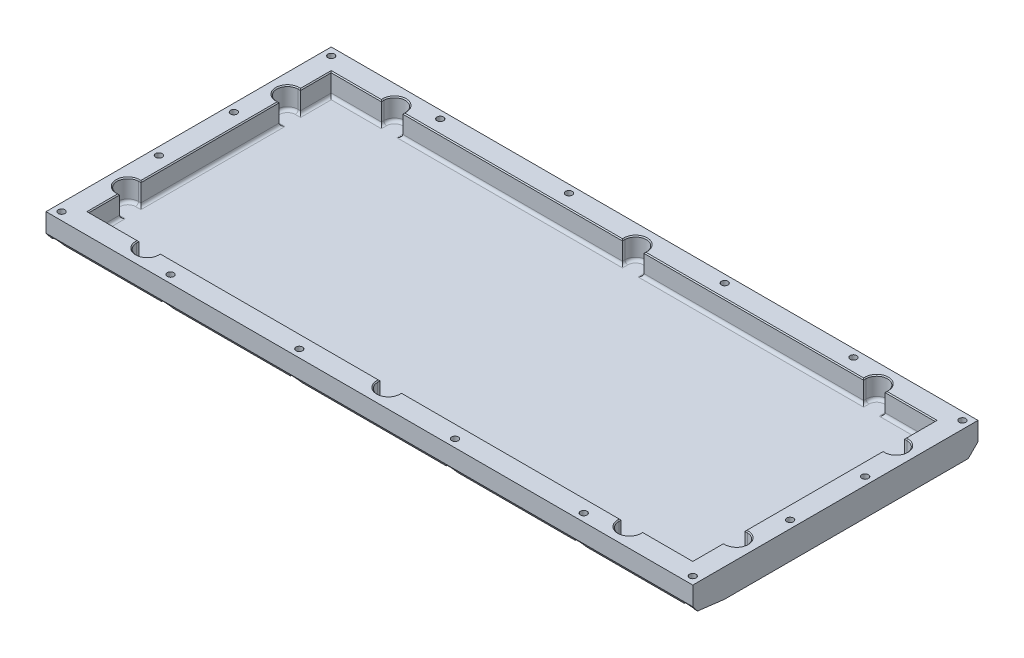
SolidWorks part; units mm, degrees
note: The reader was unsure of these and kept them because the rebuilt part matched: shared geometry of "Sketch4<3>", "Sketch6<2>".
material "7075-T6 (SN)"
ref_plane "Front Plane" through (0, 0, 0) normal (0, 0, 1) x (1, 0, 0)
ref_plane "Top Plane" through (0, 0, 0) normal (0, 1, 0) x (1, 0, 0)
ref_plane "Right Plane" through (0, 0, 0) normal (1, 0, 0) x (0, 0, -1)
sketch "Sketch1" plane through (0, 0, 0) normal (0, 1, 0) x (1, 0, 0)
  line L1 (-166.1375, 73.2688) -> (166.1375, 73.2688)
  line L2 (-166.1375, 73.2688) -> (-166.1375, -73.2688)
  line L3 (-166.1375, -73.2688) -> (166.1375, -73.2688)
  line L4 (166.1375, 73.2688) -> (166.1375, -73.2688)
  point P4 (0, 73.2688)
  point P6 (166.1375, 0)
  dimension "D1" = 146.5376
  dimension "D2" = 332.275
extrude "Boss-Extrude1" add sketch "Sketch1" against normal blind 15
sketch "Sketch4" plane through (166.1375, 0, 0) normal (1, 0, 0) x (0, 0, -1)
  line L0 (-73.2688, -12.5) -> (73.2688, -30.4926)
  line L1 (-73.2688, -15) -> (-73.2688, 0) construction
  line L2 (73.2688, -30.4926) -> (73.2688, -15)
  line L3 (73.2688, -15) -> (73.2688, 0) construction
  line L4 (-73.2688, 0) -> (73.2688, 0) construction
  line L5 (73.2688, -15) -> (-73.2688, -15)
  line L6 (-73.2688, -15) -> (-73.2688, -12.5)
  line M4 (-73.2688, 0) -> (-73.2688, -15)
  line M5 (-73.2688, -15) -> (73.2688, -15)
  dimension "D1" = 7
  dimension "D2" = 12.5
extrude "Cut-Extrude1" cut sketch "Sketch4" against normal through all contours L0 M4 M5
extrude "Boss-Extrude2" add sketch "Sketch4<3>" against normal up to surface (332.275 mm away) contours L0 L2 M5 up to face at (-166.1375, -8.5, 10.5816)
sketch "Sketch4<3>" plane through (166.1375, 0, 0) normal (1, 0, 0) x (0, 0, -1) same geometry as "Sketch4"
sketch "Sketch6" plane through (-166.1375, 0, 0) normal (-1, 0, 0) x (0, 0, 1)
  line L1 (-73.2688, 0) -> (73.2688, 0) construction
  line L3 (-73.2688, -14.5) -> (56.9801, -14.5)
  line L7 (-73.2688, 0) -> (-73.2688, -30.4926)
  line L8 (-73.2688, -30.4926) -> (73.2688, -12.5)
  line L9 (73.2688, -12.5) -> (73.2688, 0)
  line L10 (73.2688, 0) -> (-73.2688, 0)
  line L11 (-73.2688, -14.5) -> (-73.2688, -30.4926)
  line L12 (-73.2688, -30.4926) -> (56.9801, -14.5)
  point P0 (-77.4503, -15.2463)
  dimension "D1" = 14.5
  dimension "D2" = 0
extrude "Cut-Extrude3" cut sketch "Sketch6" against normal blind 75
extrude "Cut-Extrude4" cut sketch "Sketch6<2>" along normal blind 75 from surface at -332.275
sketch "Sketch6<2>" plane through (-166.1375, 0, 0) normal (-1, 0, 0) x (0, 0, 1) same geometry as "Sketch6"
chamfer "Chamfer3" distance 5 angle 45 3 edges at (128.6375, -14.5, -73.2688) (0, -30.4926, -73.2688) (-128.6375, -14.5, -73.2688)
chamfer "Chamfer4" distance 0.5 angle 45 2 edges at (91.1375, -22.2229, -5.9177) (-91.1375, -22.2229, -5.9177)
chamfer "Chamfer5" distance 2.5 angle 45 1 edges at (0, -12.5, 73.2688)
hole_wizard "M3 Clearance Hole1" positions "Sketch7" profile "Sketch8" hole size "M3" standard "DIN" end condition through all
sketch "Sketch7" plane through (0, 0, 0) normal (0, 1, 0) x (1, 0, 0)
  line L0 (166.1375, 73.2688) -> (-166.1375, 73.2688) construction
  line L1 (-166.1375, 73.2688) -> (-166.1375, -73.2688) construction
  line L2 (0, 0) -> (0, 73.2688) construction
  line L5 (0, 0) -> (-166.1375, 0) construction
  line L6 (-166.1375, -73.2688) -> (166.1375, -73.2688) construction
  point P0 (-162.1375, 69.2688)
  point P21 (-106.1375, 69.2688)
  point P23 (-40, 69.2688)
  point P28 (-162.1375, -69.2688)
  point P34 (-162.1375, -19.2688)
  point P36 (-162.1375, 19.2688)
  point P39 (0, 0)
  point P40 (0, 0)
  point P41 (162.1375, 19.2688)
  point P42 (162.1375, -19.2688)
  point P43 (162.1375, -69.2688)
  point P44 (40, 69.2688)
  point P45 (106.1375, 69.2688)
  point P46 (162.1375, 69.2688)
  point P47 (0, 0)
  point P48 (106.1375, -69.2688)
  point P49 (40, -69.2688)
  point P51 (-40, -69.2688)
  point P52 (-106.1375, -69.2688)
  point P53 (0, 0)
  point P54 (0, 0)
  dimension "D1" = 4
  dimension "D2" = 4
  dimension "D3" = 56
  dimension "D4" = 40
  dimension "D5" = 4
  dimension "D6" = 50
  dimension "D7" = 50
sketch "Sketch8" plane through (-162.1375, 0, -69.2688) normal (1, 0, 0) x (0, 0, 1)
  line L0 (0, 0) -> (0, 29.9458)
  line L1 (0, 29.9458) -> (1.7, 29.9458)
  line L2 (1.7, 29.9458) -> (1.7, 0)
  line L5 (1.7, 0) -> (0, 0)
  line L11 (0, -6.35) -> (0, 107.95) construction
  dimension "Thru Hole Dia." = 3.4
  dimension "Thru Hole Depth" = 29.9458
sketch "Sketch9" plane through (0, -14.5, 0) normal (0, -1, 0) x (1, 0, 0)
  circle A0 centre (-162.1375, 69.2688) radius 3.25
  circle A1 centre (-162.1375, 19.2688) radius 3.25
  circle A2 centre (-162.1375, -19.2688) radius 3.25
  circle A3 centre (-162.1375, -69.2688) radius 3.25
  circle A4 centre (-106.1375, -69.2688) radius 3.25
  circle A5 centre (-40, -69.2688) radius 3.25
  circle A7 centre (40, -69.2688) radius 3.25
  circle A8 centre (106.1375, -69.2688) radius 3.25
  circle A9 centre (162.1375, -69.2688) radius 3.25
  circle A10 centre (162.1375, -19.2688) radius 3.25
  circle A11 centre (162.1375, 19.2688) radius 3.25
  circle A12 centre (162.1375, 69.2688) radius 3.25
  circle A13 centre (106.1375, 69.2688) radius 3.25
  circle A14 centre (40, 69.2688) radius 3.25
  circle A16 centre (-40, 69.2688) radius 3.25
  circle A17 centre (-106.1375, 69.2688) radius 3.25
  dimension "D1" = 6.5
extrude "Cut-Extrude5" cut sketch "Sketch9" against normal offset from surface 4 and the other way through all up to face at (-162.1375, 0, -67.5688)
fillet "Fillet2" radius 3 2 edges at (91.1375, -14.5, -7.6957) (-91.1375, -14.5, -7.6957)
sketch "Sketch5" plane through (0, 0, 1.305) normal (0, -1, 0) x (1, 0, 0)
  line L0 (166.1375, -74.5738) -> (-166.1375, -74.5738) construction
  line L1 (-155.1375, -63.5738) -> (155.1375, -63.5738)
  line L2 (-155.1375, -63.5738) -> (-155.1375, 60.9638)
  line L3 (-155.1375, 60.9638) -> (155.1375, 60.9638)
  line L4 (155.1375, -63.5738) -> (155.1375, 60.9638)
  line L5 (-166.1375, -74.5738) -> (-166.1375, 71.9638) construction
  point P4 (0, -63.5738)
  point P6 (155.1375, -1.305)
  dimension "D1" = 11
  dimension "D2" = 11
extrude "Cut-Extrude2" cut sketch "Sketch5" along normal blind 11 from surface at 0 starting at face at (-162.1375, 0, -67.5688)
sketch "Sketch10" plane through (0, 0, 0) normal (0, 1, 0) x (1, 0, 0)
  line L0 (-129.375, 63.5063) -> (-129.375, 62.2688)
  line L1 (155.1375, 62.2688) -> (-155.1375, 62.2688) construction
  line L2 (-129.375, 62.2688) -> (-118.375, 62.2688)
  line L3 (-118.375, 62.2688) -> (-118.375, 63.5063)
  line L4 (-156.375, 46.5063) -> (-155.1375, 46.5063)
  line L5 (-155.1375, 62.2688) -> (-155.1375, -62.2688) construction
  line L6 (-155.1375, 46.5063) -> (-155.1375, 35.5063)
  line L7 (-155.1375, 62.2688) -> (-155.1375, -62.2688) construction
  line L8 (-155.1375, 35.5063) -> (-156.375, 35.5063)
  line L9 (-5.5, 63.5063) -> (-5.5, 62.2688)
  line L10 (-5.5, 62.2688) -> (5.5, 62.2688)
  line L11 (5.5, 62.2688) -> (5.5, 63.5063)
  line L12 (129.375, 63.5063) -> (129.375, 62.2688)
  line L13 (129.375, 62.2688) -> (118.375, 62.2688)
  line L14 (118.375, 62.2688) -> (118.375, 63.5063)
  line L15 (156.375, 46.5063) -> (155.1375, 46.5063)
  line L16 (155.1375, -62.2688) -> (155.1375, 62.2688) construction
  line L17 (155.1375, 46.5063) -> (155.1375, 35.5063)
  line L18 (155.1375, -62.2688) -> (155.1375, 62.2688) construction
  line L19 (155.1375, 35.5063) -> (156.375, 35.5063)
  line L20 (156.375, -35.5062) -> (155.1375, -35.5062)
  line L21 (155.1375, -35.5062) -> (155.1375, -46.5062)
  line L22 (155.1375, -46.5062) -> (156.375, -46.5062)
  line L23 (129.375, -63.5062) -> (129.375, -62.2688)
  line L24 (-155.1375, -62.2688) -> (155.1375, -62.2688) construction
  line L25 (129.375, -62.2688) -> (118.375, -62.2688)
  line L26 (118.375, -62.2688) -> (118.375, -63.5062)
  line L27 (-5.5, -63.5062) -> (-5.5, -62.2688)
  line L28 (-5.5, -62.2688) -> (5.5, -62.2688)
  line L29 (5.5, -62.2688) -> (5.5, -63.5062)
  line L30 (-129.375, -63.5062) -> (-129.375, -62.2688)
  line L31 (-129.375, -62.2688) -> (-118.375, -62.2688)
  line L32 (-118.375, -62.2688) -> (-118.375, -63.5062)
  line L33 (-156.375, -46.5062) -> (-155.1375, -46.5062)
  line L34 (-155.1375, -46.5062) -> (-155.1375, -35.5062)
  line L35 (-155.1375, -35.5062) -> (-156.375, -35.5062)
  arc A16 (-156.375, 46.5063) -> (-156.375, 35.5063) centre (-156.375, 41.0063) ccw
  arc A17 (-156.375, 46.5063) -> (-156.375, 35.5063) centre (-156.375, 41.0063) ccw
  arc A19 (-118.375, 63.5063) -> (-129.375, 63.5063) centre (-123.875, 63.5063) ccw
  arc A20 (-118.375, 63.5063) -> (-129.375, 63.5063) centre (-123.875, 63.5063) ccw
  arc A22 (-156.375, -35.5062) -> (-156.375, -46.5062) centre (-156.375, -41.0062) ccw
  arc A23 (-156.375, -35.5062) -> (-156.375, -46.5062) centre (-156.375, -41.0062) ccw
  arc A25 (-129.375, -63.5062) -> (-118.375, -63.5062) centre (-123.875, -63.5062) ccw
  arc A26 (-129.375, -63.5062) -> (-118.375, -63.5062) centre (-123.875, -63.5062) ccw
  arc A28 (-5.5, -63.5062) -> (5.5, -63.5062) centre (0, -63.5062) ccw
  arc A29 (-5.5, -63.5062) -> (5.5, -63.5062) centre (0, -63.5062) ccw
  arc A31 (5.5, 63.5063) -> (-5.5, 63.5063) centre (0, 63.5063) ccw
  arc A32 (5.5, 63.5063) -> (-5.5, 63.5063) centre (0, 63.5063) ccw
  arc A34 (129.375, 63.5063) -> (118.375, 63.5063) centre (123.875, 63.5063) ccw
  arc A35 (129.375, 63.5063) -> (118.375, 63.5063) centre (123.875, 63.5063) ccw
  arc A37 (156.375, 35.5063) -> (156.375, 46.5063) centre (156.375, 41.0063) ccw
  arc A38 (156.375, 35.5063) -> (156.375, 46.5063) centre (156.375, 41.0063) ccw
  arc A40 (118.375, -63.5062) -> (129.375, -63.5062) centre (123.875, -63.5062) ccw
  arc A41 (118.375, -63.5062) -> (129.375, -63.5062) centre (123.875, -63.5062) ccw
  arc A43 (156.375, -46.5062) -> (156.375, -35.5062) centre (156.375, -41.0062) ccw
  arc A44 (156.375, -46.5062) -> (156.375, -35.5062) centre (156.375, -41.0062) ccw
  dimension "D1" = 1
  dimension "D2" = 1
  dimension "D3" = 1
  dimension "D4" = 1
  dimension "D5" = 1
  dimension "D6" = 1
  dimension "D7" = 1
  dimension "D8" = 1
  dimension "D9" = 1
  dimension "D10" = 1
extrude "Cut-Extrude7" cut sketch "Sketch10" against normal up to surface (11 mm away) up to face at (0, -11, 0)
fillet "Fillet3" radius 1.5 44 edges at (129.375, -11, 62.8875) (123.875, -11, 69.0062) (118.375, -11, 62.8875) (61.9375, -11, 62.2688) (5.5, -11, 62.8875) (0, -11, 69.0062) (-5.5, -11, 62.8875) (-61.9375, -11, 62.2688) (-118.375, -11, 62.8875) (-123.875, -11, 69.0062) (-129.375, -11, 62.8875) (-142.2562, -11, 62.2688) (-155.1375, -11, 54.3875) (-155.7562, -11, 46.5062) (-161.875, -11, 41.0062) (-155.7562, -11, 35.5062) (-155.1375, -11, 0) (-155.7562, -11, -35.5063) (-161.875, -11, -41.0063) (-155.7562, -11, -46.5063) (-155.1375, -11, -54.3875) (-142.2562, -11, -62.2688) (-129.375, -11, -62.8875) (-123.875, -11, -69.0063) (-118.375, -11, -62.8875) (-61.9375, -11, -62.2688) (-5.5, -11, -62.8875) (0, -11, -69.0063) (5.5, -11, -62.8875) (61.9375, -11, -62.2688) (118.375, -11, -62.8875) (123.875, -11, -69.0063) (129.375, -11, -62.8875) (142.2563, -11, -62.2688) (155.1375, -11, -54.3875) (155.7562, -11, -46.5063) (161.875, -11, -41.0063) (155.7562, -11, -35.5063) (155.1375, -11, 0) (155.7562, -11, 35.5062) (161.875, -11, 41.0062) (155.7562, -11, 46.5062) (155.1375, -11, 54.3875) (142.2563, -11, 62.2688)
chamfer "Chamfer7" distance 0.5 angle 45 44 edges at (-123.875, 0, -69.0063) (-129.375, 0, -62.8875) (-142.2562, 0, -62.2688) (-155.1375, 0, -54.3875) (-155.7562, 0, -46.5063) (-161.875, 0, -41.0063) (-155.7562, 0, -35.5063) (-155.1375, 0, 0) (-155.7562, 0, 35.5062) (-161.875, 0, 41.0062) (-155.7562, 0, 46.5062) (-155.1375, 0, 54.3875) (-142.2562, 0, 62.2688) (-129.375, 0, 62.8875) (-123.875, 0, 69.0062) (-118.375, 0, 62.8875) (-61.9375, 0, 62.2688) (-5.5, 0, 62.8875) (0, 0, 69.0062) (5.5, 0, 62.8875) (61.9375, 0, 62.2688) (118.375, 0, 62.8875) (123.875, 0, 69.0062) (129.375, 0, 62.8875) (142.2563, 0, 62.2688) (155.1375, 0, 54.3875) (155.7562, 0, 46.5062) (161.875, 0, 41.0062) (155.7562, 0, 35.5062) (155.1375, 0, 0) (155.7562, 0, -35.5063) (161.875, 0, -41.0063) (155.7562, 0, -46.5063) (155.1375, 0, -54.3875) (142.2563, 0, -62.2688) (129.375, 0, -62.8875) (123.875, 0, -69.0063) (118.375, 0, -62.8875) (61.9375, 0, -62.2688) (5.5, 0, -62.8875) (0, 0, -69.0063) (-5.5, 0, -62.8875) (-61.9375, 0, -62.2688) (-118.375, 0, -62.8875)
